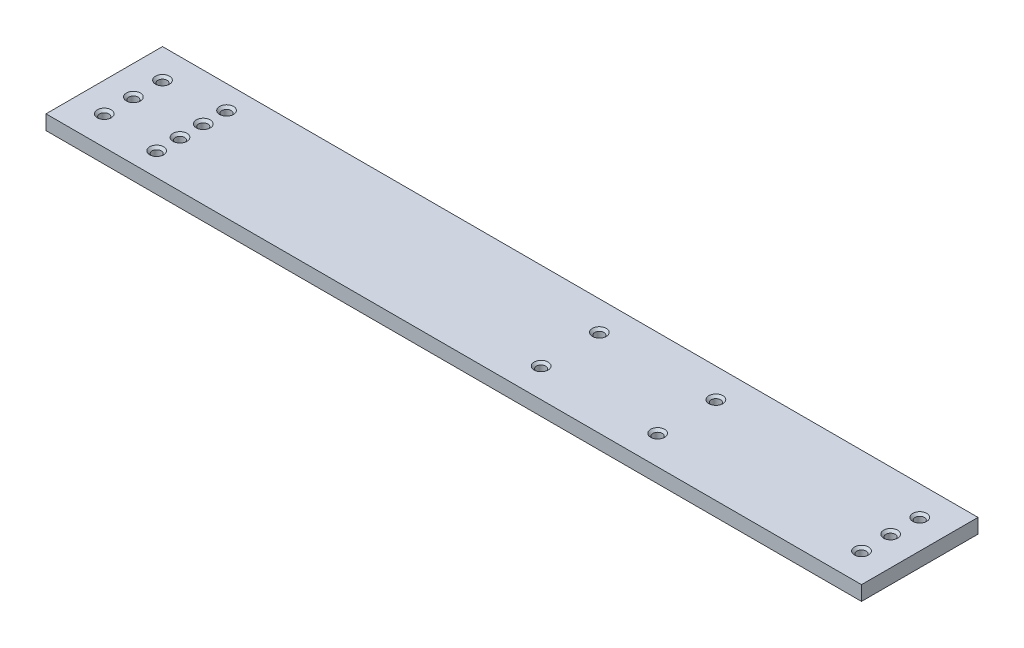
SolidWorks part; units mm, degrees
material "6061-T6 (SS)"
ref_plane "Front" through (0, 0, 0) normal (0, 0, 1) x (1, 0, 0)
ref_plane "Top" through (0, 0, 0) normal (0, 1, 0) x (1, 0, 0)
ref_plane "Right" through (0, 0, 0) normal (1, 0, 0) x (0, 0, -1)
sketch "Sketch1" plane through (0, 0, 0) normal (0, 1, 0) x (1, 0, 0)
  line L1 (-177.8, -25.4) -> (177.8, -25.4)
  line L2 (-177.8, -25.4) -> (-177.8, 25.4)
  line L3 (-177.8, 25.4) -> (177.8, 25.4)
  line L4 (177.8, -25.4) -> (177.8, 25.4)
  line L5 (-177.8, -25.4) -> (177.8, 25.4) construction
  line L6 (-177.8, 25.4) -> (177.8, -25.4) construction
  point P0 (0, 0)
  dimension "D1" = 50.8
  dimension "D2" = 355.6
extrude "Boss-Extrude1" add sketch "Sketch1" along normal blind 6.35
hole_wizard "#10-32 Tapped Hole1" positions "Sketch2" profile "Sketch4" tap size "#10-32" standard "ANSI Inch" end condition through all
sketch "Sketch2" plane through (0, 6.35, 0) normal (0, 1, 0) x (1, 0, 0)
  line L1 (-165.1, 25.4) -> (-165.1, 12.7) construction
  line L2 (177.8, 25.4) -> (-177.8, 25.4) construction
  line L3 (-165.1, 12.7) -> (-165.1, 0) construction
  line L4 (-165.1, 0) -> (-165.1, -12.7) construction
  line L5 (-165.1, -12.7) -> (-165.1, -25.4) construction
  line L6 (-177.8, -25.4) -> (177.8, -25.4) construction
  line L8 (-177.8, 25.4) -> (-177.8, -25.4) construction
  line L9 (-165.1, 0) -> (-177.8, 0) construction
  line L11 (165.1, 0) -> (177.8, 0) construction
  line L12 (177.8, -25.4) -> (177.8, 25.4) construction
  line L15 (25.4, 12.7) -> (25.4, 25.4) construction
  line L17 (25.4, -12.7) -> (25.4, -25.4) construction
  line L18 (-139.7, -25.4) -> (-139.7, -15.24) construction
  line L20 (-139.7, 5.08) -> (-139.7, 15.24) construction
  line L21 (-139.7, 15.24) -> (-139.7, 25.4) construction
  line L22 (-139.7, 5.08) -> (-139.7, -5.08) construction
  line L23 (-139.7, -5.08) -> (-139.7, -15.24) construction
  point P0 (-165.1, 12.7)
  point P2 (-165.1, 0)
  point P4 (-165.1, -12.7)
  point P6 (165.1, 12.7)
  point P8 (165.1, 0)
  point P10 (165.1, -12.7)
  point P64 (25.4, 12.7)
  point P66 (76.2, 12.7)
  point P68 (25.4, -12.7)
  point P70 (76.2, -12.7)
  point P92 (-139.7, 15.24)
  point P94 (-139.7, 5.08)
  point P102 (-139.7, -15.24)
  point P127 (-139.7, -5.08)
  dimension "D1" = 12.7
  dimension "D2" = 50.8
  dimension "D3" = 25.4
  dimension "D4" = 101.6
  dimension "D5" = 38.1
sketch "Sketch4" plane through (-165.1, 6.35, -12.7) normal (1, 0, 0) x (0, 0, 1)
  line L0 (0, 0) -> (0, 6.35)
  line L1 (0, 6.35) -> (2.0193, 6.35)
  line L2 (2.0193, 6.35) -> (2.0193, 1.0287)
  line L3 (2.0193, 1.0287) -> (3.048, 0)
  line L5 (3.048, 0) -> (0, 0)
  line L6 (-2.0193, 1.0287) -> (-3.048, 0) construction
  line L11 (0, -6.35) -> (0, 107.95) construction
  dimension "Thru Tap Drill Dia." = 4.0386
  dimension "Thru Tap Drill Depth" = 6.35
  dimension "Near C'Sink Dia." = 6.096
  dimension "Near C'Sink Angle" = 90
cosmetic thread "Hole Thread3" parameters "D2"=4.826
cosmetic thread "Hole Thread4" parameters "D2"=4.826
cosmetic thread "Hole Thread5" parameters "D2"=4.826
cosmetic thread "Hole Thread6" parameters "D2"=4.826
cosmetic thread "Hole Thread7" parameters "D2"=4.826
cosmetic thread "Hole Thread9" parameters "D2"=4.826
cosmetic thread "Hole Thread10" parameters "D2"=4.826
cosmetic thread "Hole Thread11" parameters "D2"=4.826
cosmetic thread "Hole Thread12" parameters "D2"=4.826
cosmetic thread "Hole Thread13" parameters "D2"=4.826
cosmetic thread "Hole Thread15" parameters "D2"=4.826
cosmetic thread "Hole Thread16" parameters "D2"=4.826
cosmetic thread "Hole Thread17" parameters "D2"=4.826
cosmetic thread "Hole Thread18" parameters "D2"=4.826
